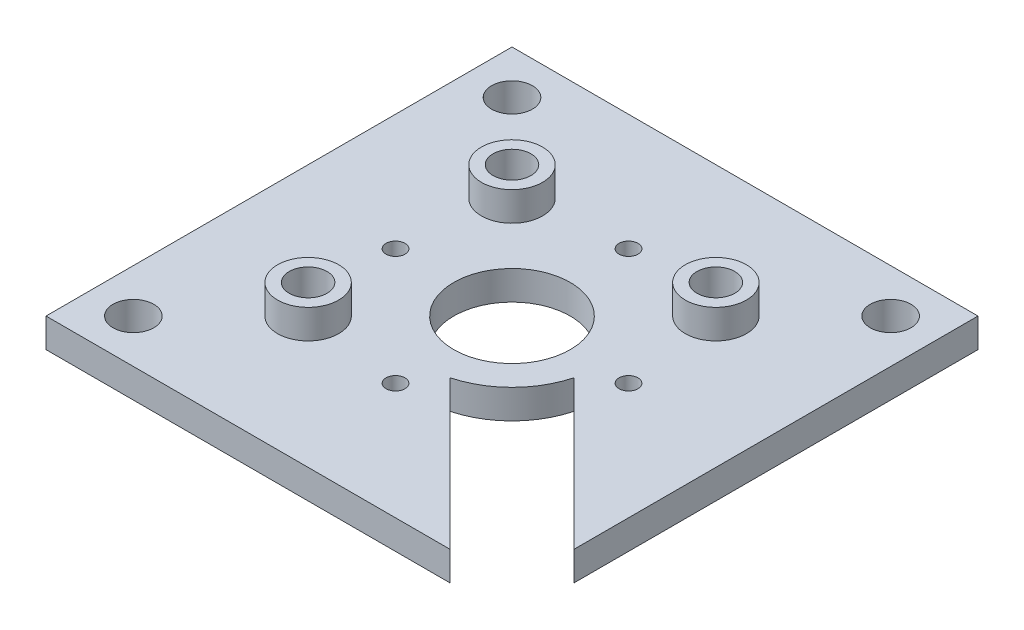
SolidWorks part; units mm, degrees
ref_plane "前视基准面" through (0, 0, 0) normal (0, 0, 1) x (1, 0, 0)
ref_plane "上视基准面" through (0, 0, 0) normal (0, 1, 0) x (1, 0, 0)
ref_plane "右视基准面" through (0, 0, 0) normal (1, 0, 0) x (0, 0, -1)
sketch "草图1" plane through (0, 0, 0) normal (0, 1, 0) x (1, 0, 0)
  line L0 (0, 0) -> (8, 0) construction
  line L1 (0, 0) -> (0, 8) construction
  line L3 (-16, 16) -> (16, 16)
  line L4 (-16, 16) -> (-16, -16)
  line L5 (-16, -16) -> (16, -16)
  line L6 (16, 16) -> (16, -16)
  circle A0 centre (0, 0) radius 8 construction
  circle A1 centre (8, 0) radius 0.65
  circle A2 centre (0, -8) radius 0.65
  circle A3 centre (-8, 0) radius 0.65
  circle A4 centre (0, 8) radius 0.65
  circle A5 centre (0, 0) radius 4
  circle A6 centre (0, 0) radius 16 construction
  circle A7 centre (13, 13) radius 1.4
  circle A8 centre (-13, 13) radius 1.4
  circle A9 centre (13, -13) radius 1.4
  circle A10 centre (-13, -13) radius 1.4
  dimension "D1" = 16
  dimension "D2" = 1.3
  dimension "D4" = 8
  dimension "D5" = 32
  dimension "D6" = 2.8
  dimension "D7" = 26
  dimension "D8" = 26
  dimension "D3" = 4
extrude "凸台-拉伸1" add sketch "草图1" along normal blind 2 contours L6 L3 L4 L5 A10 A8 A7 A5 A4 A3 A2 A1 A9 region at (0, 0, -15.5475)
sketch "草图2" plane through (0, 2, 0) normal (0, 1, 0) x (1, 0, 0)
  line L0 (0, 0) -> (7, 7) construction
  line L1 (0, 0) -> (9.8995, 0) construction
  line L2 (5.7956, -1.5529) -> (16, -11.7574)
  line L3 (16, 16) -> (16, -16) construction
  line L4 (0, 0) -> (16, -16) construction
  line L5 (1.5529, -5.7956) -> (11.7574, -16)
  line L6 (16, -11.7574) -> (16, -16)
  line L7 (16, -16) -> (11.7574, -16)
  circle A0 centre (0, 0) radius 9.8995 construction
  circle A1 centre (7, 7) radius 1.3
  circle A2 centre (7, 7) radius 2.1
  circle A3 centre (7, -7) radius 2.1
  circle A4 centre (7, -7) radius 1.3
  circle A5 centre (-7, -7) radius 2.1
  circle A6 centre (-7, -7) radius 1.3
  circle A7 centre (-7, 7) radius 2.1
  circle A8 centre (-7, 7) radius 1.3
  circle A9 centre (0, 0) radius 6 construction
  arc A10 (5.7956, -1.5529) -> (1.5529, -5.7956) centre (0, 0) cw
  line M20 (16, -16) -> (16, 16)
  line M23 (-16, -16) -> (16, -16)
  circle M24 centre (13, -13) radius 1.4
  dimension "D1" = 2.6
  dimension "D2" = 4.2
  dimension "D6" = 12
  dimension "D4" = 45
  dimension "D5" = 14
  dimension "D7" = 6
  dimension "D3" = 4
extrude "凸台-拉伸3" add sketch "草图2" along normal blind 2 contours A5 A6 | A7 A8 | A2 A1 region at (4.9594, 2, -7) region at (-9.0406, 2, 7) region at (-9.0406, 2, -7)
extrude "切除-拉伸2" cut sketch "草图2<6>" against normal up to surface (2 mm away) contours A8 | A6 | A1 | A3 A4 | A4 | L2 A10 L5 A3 M23 M20 M24 region at (9.7, 2, 9.7) region at (7, 2, -7) region at (4.9594, 2, 7) region at (7, 2, 7) region at (-7, 2, 7) region at (-7, 2, -7) up to face at (-13, 0, 14.4)
sketch "草图2<6>" plane through (0, 2, 0) normal (0, 1, 0) x (1, 0, 0) same geometry as "草图2"
